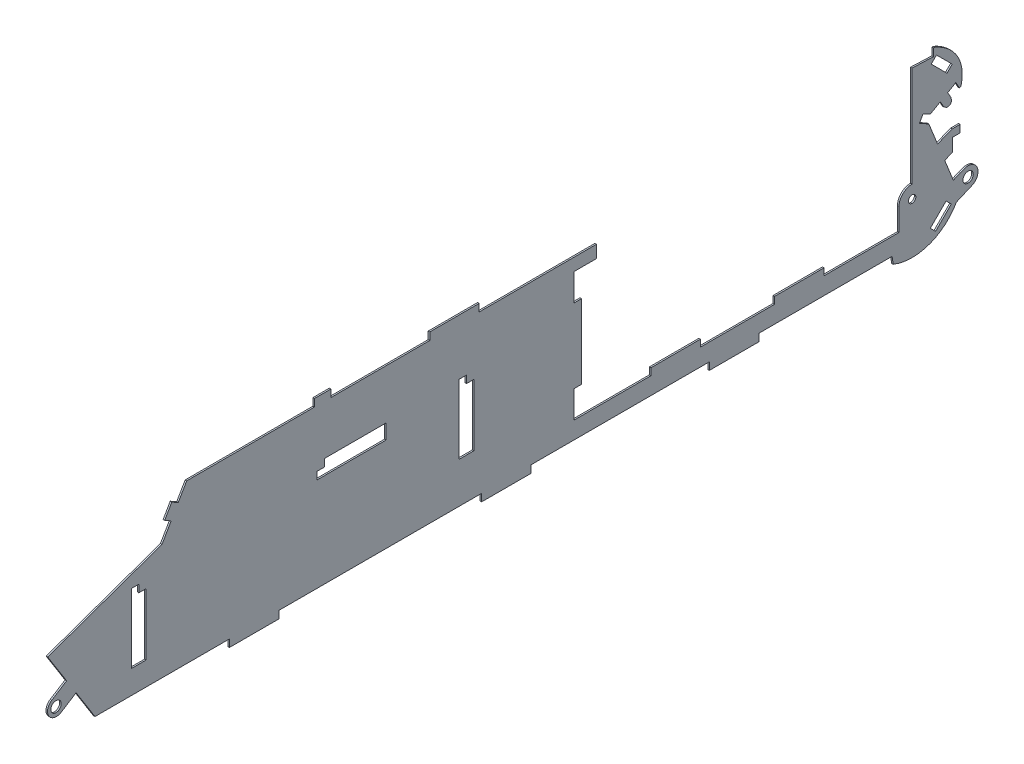
SolidWorks part; units mm, degrees
ref_plane "Front Plane" through (0, 0, 0) normal (0, 0, 1) x (1, 0, 0)
ref_plane "Top Plane" through (0, 0, 0) normal (0, 1, 0) x (1, 0, 0)
ref_plane "Right Plane" through (0, 0, 0) normal (1, 0, 0) x (0, 0, -1)
sketch "Sketch1" plane through (0, 0, 0) normal (1, 0, 0) x (0, 0, -1)
  line L206 (885.0364, -68.4875) -> (876.0357, -71.8807)
  line L207 (876.0357, -71.8807) -> (862.593, -77.4416)
  line L208 (862.593, -77.4416) -> (845.7137, -35.431)
  line L209 (845.7137, -35.431) -> (859.2198, -30.0085)
  line L210 (859.2198, -30.0085) -> (861.2307, -29.1365)
  line L211 (861.2307, -29.1365) -> (861.2874, -3.9151)
  line L212 (861.2874, -3.9151) -> (875.8073, -3.9151)
  line L213 (875.8073, -3.9151) -> (875.8073, 10.6048)
  line L214 (875.8073, 10.6048) -> (861.2874, 10.6048)
  line L215 (861.2874, 10.6048) -> (860.2336, 10.6048)
  line L216 (860.2336, 10.6048) -> (831.7958, -0.777)
  line L217 (831.7958, -0.777) -> (814.633, 41.9406)
  line L218 (814.633, 41.9406) -> (796.3664, 51.9634)
  line L219 (796.3664, 51.9634) -> (803.3529, 64.6925)
  line L220 (803.3529, 64.6925) -> (817.3993, 56.989)
  line L221 (817.3993, 56.989) -> (837.1348, 68.1974)
  line L222 (837.1348, 68.1974) -> (844.3497, 55.5467)
  line L223 (844.3497, 55.5467) -> (845.3402, 56.1086)
  line L224 (857.9059, 63.2635) -> (858.7529, 63.7471)
  line L225 (858.7529, 63.7471) -> (851.543, 76.3761)
  line L226 (851.543, 76.3761) -> (864.5972, 83.7994)
  line L227 (864.5972, 83.7994) -> (867.3351, 85.7303)
  line L228 (867.3351, 85.7303) -> (874.595, 72.7761)
  line L229 (874.595, 72.7761) -> (877.5414, 74.4469)
  line L230 (826.7451, 165.7947) -> (824.0506, 165.9198)
  line L231 (824.0506, 165.9198) -> (823.4837, 151.4082)
  line L232 (823.4837, 151.4082) -> (823.4036, 151.3932)
  line L233 (823.4036, 151.3932) -> (781.9216, 153.009)
  line L234 (781.9216, 153.009) -> (781.9216, -43.5713)
  line L235 (756.17, -69.3229) -> (756.17, -112.8509)
  line L236 (756.17, -112.8509) -> (609.6406, -112.8292)
  line L237 (609.6406, -112.8292) -> (609.6406, -99.3431)
  line L238 (609.6406, -99.3431) -> (512.8487, -99.3431)
  line L239 (512.8487, -99.3431) -> (512.8487, -112.8292)
  line L240 (512.8487, -112.8292) -> (367.6465, -112.8292)
  line L241 (367.6465, -112.8292) -> (367.6465, -99.3464)
  line L242 (367.6465, -99.3464) -> (270.8496, -99.3464)
  line L243 (270.8496, -99.3464) -> (270.8496, -112.8309)
  line L244 (270.8496, -112.8309) -> (120.7953, -112.8309)
  line L245 (120.7953, -112.8309) -> (120.7953, -59.5902)
  line L246 (120.7953, -59.5902) -> (135.3085, -59.5902)
  line L247 (135.3085, -59.5902) -> (135.3085, 85.6069)
  line L248 (135.3085, 85.6069) -> (120.7869, 85.6069)
  line L249 (120.7869, 85.6069) -> (120.7869, 138.8526)
  line L250 (120.7869, 138.8526) -> (164.0748, 138.8526)
  line L251 (164.0748, 138.8526) -> (164.2682, 163.2136)
  line L252 (164.2682, 163.2136) -> (-64.9935, 163.2136)
  line L253 (-64.9935, 163.2136) -> (-64.9935, 177.7334)
  line L254 (-64.9935, 177.7334) -> (-161.7921, 177.7334)
  line L255 (-161.7921, 177.7334) -> (-161.7921, 163.2136)
  line L256 (-161.7921, 163.2136) -> (-355.391, 163.2136)
  line L257 (-355.391, 163.2136) -> (-355.391, 177.7334)
  line L258 (-355.391, 177.7334) -> (-387.4321, 177.7334)
  line L259 (-387.4321, 177.7334) -> (-387.4321, 163.2136)
  line L260 (-387.4321, 163.2136) -> (-637.3715, 163.2136)
  line L261 (-637.3715, 163.2136) -> (-653.9739, 134.5156)
  line L262 (-653.9739, 134.5156) -> (-666.5396, 141.7906)
  line L263 (-666.5396, 141.7906) -> (-680.4125, 117.8164)
  line L264 (-680.4125, 117.8164) -> (-667.8469, 110.5365)
  line L265 (-667.8469, 110.5365) -> (-685.7032, 79.6792)
  line L266 (-685.7032, 79.6792) -> (-909.3424, 0.6836)
  line L267 (-909.3424, 0.6836) -> (-872.3257, -58.2046)
  line L268 (-872.3257, -58.2046) -> (-901.3971, -76.5678)
  line L269 (-882.9438, -106.2229) -> (-853.769, -87.7245)
  line L270 (-853.769, -87.7245) -> (-816.799, -146.5411)
  line L271 (-816.799, -146.5411) -> (-553.7821, -146.5411)
  line L272 (-553.7821, -146.5411) -> (-553.7821, -161.0209)
  line L273 (-553.7821, -161.0209) -> (-456.9818, -161.0209)
  line L274 (-456.9818, -161.0209) -> (-456.9818, -146.5411)
  line L275 (-456.9818, -146.5411) -> (-60.0996, -146.5411)
  line L276 (-60.0996, -146.5411) -> (-60.0996, -161.0209)
  line L277 (-60.0996, -161.0209) -> (36.6974, -161.0209)
  line L278 (36.6974, -161.0209) -> (36.6974, -146.5411)
  line L279 (36.6974, -146.5411) -> (385.1761, -146.5411)
  line L280 (385.1761, -146.5411) -> (385.1761, -161.0593)
  line L281 (385.1761, -161.0593) -> (481.9747, -161.0593)
  line L282 (481.9747, -161.0593) -> (481.9747, -146.5411)
  line L283 (481.9747, -146.5411) -> (742.7439, -146.5411)
  line L284 (742.7439, -146.5411) -> (744.9066, -161.0593)
  line L285 (868.5423, -117.643) -> (898.7459, -104.7005)
  line L286 (774.7951, -69.0978) -> (774.7951, -69.0945)
  line L287 (829.6281, 151.1581) -> (860.4287, 120.3542)
  line L288 (860.4287, 120.3542) -> (850.1624, 110.0863)
  line L289 (850.1624, 110.0863) -> (819.3585, 140.8885)
  line L290 (819.3585, 140.8885) -> (829.6281, 151.1581)
  line L291 (-716.5505, -100.7154) -> (-745.5902, -100.7154)
  line L292 (-745.5902, -100.7154) -> (-745.5902, 34.804)
  line L293 (-745.5902, 34.804) -> (-731.0704, 34.804)
  line L294 (-731.0704, 34.804) -> (-731.0704, 20.2841)
  line L295 (-731.0704, 20.2841) -> (-716.5521, 20.2841)
  line L296 (-716.5521, 20.2841) -> (-716.5505, -100.7154)
  line L297 (-247.0705, 37.2234) -> (-382.5883, 37.2234)
  line L298 (-382.5883, 37.2234) -> (-382.5883, 51.7433)
  line L299 (-382.5883, 51.7433) -> (-368.0684, 51.7433)
  line L300 (-368.0684, 51.7433) -> (-368.0684, 66.2615)
  line L301 (-368.0684, 66.2615) -> (-247.0705, 66.2615)
  line L302 (-247.0705, 66.2615) -> (-247.0705, 37.2234)
  line L303 (-75.2498, -66.8351) -> (-104.2912, -66.8351)
  line L304 (-104.2912, -66.8351) -> (-104.2912, 68.6826)
  line L305 (-104.2912, 68.6826) -> (-89.7713, 68.6826)
  line L306 (-89.7713, 68.6826) -> (-89.7713, 54.1627)
  line L307 (-89.7713, 54.1627) -> (-75.2531, 54.1627)
  line L308 (-75.2531, 54.1627) -> (-75.2531, -66.8351)
  line L309 (-75.2531, -66.8351) -> (-75.2498, -66.8351)
  line L310 (827.8323, -146.6161) -> (817.5627, -136.3498)
  line L311 (817.5627, -136.3498) -> (848.3666, -105.5476)
  line L312 (848.3666, -105.5476) -> (858.6328, -115.8139)
  line L313 (858.6328, -115.8139) -> (827.8323, -146.6161)
  spline S4 degree 3 poles (891.481, -67.3837) (889.2216, -67.3837) (887.049, -67.7755) (885.0364, -68.4875) knots 0 0 0 0 1 1 1 1
  spline S5 degree 3 poles (845.3402, 56.1086) (846.5774, 53.8609) (848.9318, 52.3069) (851.683, 52.3069) knots 19 19 19 19 20 20 20 20
  spline S6 degree 3 poles (851.683, 52.3069) (855.6982, 52.3069) (858.943, 55.5584) (858.943, 59.5668) knots 20 20 20 20 21 21 21 21
  spline S7 degree 3 poles (858.943, 59.5668) (858.943, 60.9225) (858.5511, 62.178) (857.9059, 63.2635) knots 21 21 21 21 22 22 22 22
  spline S8 degree 3 poles (877.5414, 74.4469) (889.0666, 122.0417) (856.1984, 153.6292) (826.7451, 165.7947) knots 28 28 28 28 29 29 29 29
  spline S9 degree 3 poles (781.9216, -43.5713) (767.6985, -43.5713) (756.17, -55.1032) (756.17, -69.3229) knots 34 34 34 34 35 35 35 35
  spline S10 degree 3 poles (-901.3971, -76.5678) (-909.5875, -81.6601) (-912.0953, -92.435) (-906.9996, -100.6254) knots 69 69 69 69 70 70 70 70
  spline S11 degree 3 poles (-906.9996, -100.6254) (-901.904, -108.8157) (-891.1342, -111.3252) (-882.9438, -106.2229) knots 70 70 70 70 71 71 71 71
  spline S12 degree 3 poles (744.9066, -161.0593) (756.3934, -165.7047) (768.9191, -168.2825) (782.0633, -168.2825) knots 87 87 87 87 88 88 88 88
  spline S13 degree 3 poles (782.0633, -168.2825) (819.2034, -168.2825) (851.5613, -147.8633) (868.5423, -117.643) knots 88 88 88 88 89 89 89 89
  spline S14 degree 3 poles (898.7459, -104.7005) (905.8391, -101.8209) (910.838, -94.8728) (910.8414, -86.7491) knots 90 90 90 90 91 91 91 91
  spline S15 degree 3 poles (910.8414, -86.7491) (910.838, -76.0476) (902.1725, -67.3837) (891.481, -67.3837) knots 91 91 91 91 92 92 92 92
  spline S16 degree 3 poles (-893.0183, -81.4517) (-887.4175, -81.4517) (-882.8804, -85.9904) (-882.8804, -91.5913) (-882.8804, -97.1971) (-887.4192, -101.7292) (-893.0183, -101.7292) knots 2 2 2 2 3 3 3 4 4 4 4
  spline S17 degree 3 poles (-893.0183, -101.7292) (-898.6175, -101.7292) (-903.1579, -97.1971) (-903.1579, -91.5913) (-903.1579, -85.9938) (-898.6192, -81.4517) (-893.0183, -81.4517) knots 0 0 0 0 1 1 1 2 2 2 2
  spline S18 degree 3 poles (789.3149, -69.0945) (789.3149, -73.108) (786.0651, -76.3578) (782.055, -76.3578) knots 1 1 1 1 2 2 2 2
  spline S19 degree 3 poles (782.055, -76.3578) (778.0432, -76.3578) (774.7951, -73.108) (774.7951, -69.0978) knots 2 2 2 2 3 3 3 3
  spline S20 degree 3 poles (774.7951, -69.0945) (774.7951, -65.0793) (778.0432, -61.8345) (782.055, -61.8345) knots 5 5 5 5 6 6 6 6
  spline S21 degree 3 poles (782.055, -61.8345) (786.0635, -61.8345) (789.3149, -65.0843) (789.3149, -69.0945) knots 6 6 6 6 7 7 7 7
  spline S22 degree 2 poles (789.3149, -69.0928) (789.3149, -69.0928) (789.3149, -69.0945) knots 7.5 7.5 7.5 8 8 8
  spline S23 degree 2 poles (789.3149, -69.0945) (789.3149, -69.0928) (789.3149, -69.0928) knots 7 7 7 7.5 7.5 7.5
  spline S24 degree 3 poles (891.481, -76.6412) (897.0652, -76.6412) (901.5905, -81.1599) (901.5905, -86.7508) (901.5905, -92.3316) (897.0602, -96.8553) (891.481, -96.8553) knots 2 2 2 2 3 3 3 4 4 4 4
  spline S25 degree 3 poles (891.481, -96.8553) (885.8968, -96.8553) (881.3731, -92.3316) (881.3731, -86.7508) (881.3731, -81.1649) (885.8918, -76.6412) (891.481, -76.6412) knots 0 0 0 0 1 1 1 2 2 2 2
extrude "Boss-Extrude1" add sketch "Sketch1" along normal blind 3 contours S14 S15 S4 L206 L207 L208 L209 L210 L211 L212 L213 L214 L215 L216 L217 L218 L219 L220 L221 L222 L223 S5 S6 S7 L224 L225 L226 L227 L228 L229 S8 L230 L231 L232 L233 L234 S9 L235 L236 L237 L238 L239 L240 L241 L242 L243 L244 L245 L246 L247 L248 region at (0, -10.5688, 185.0314)
